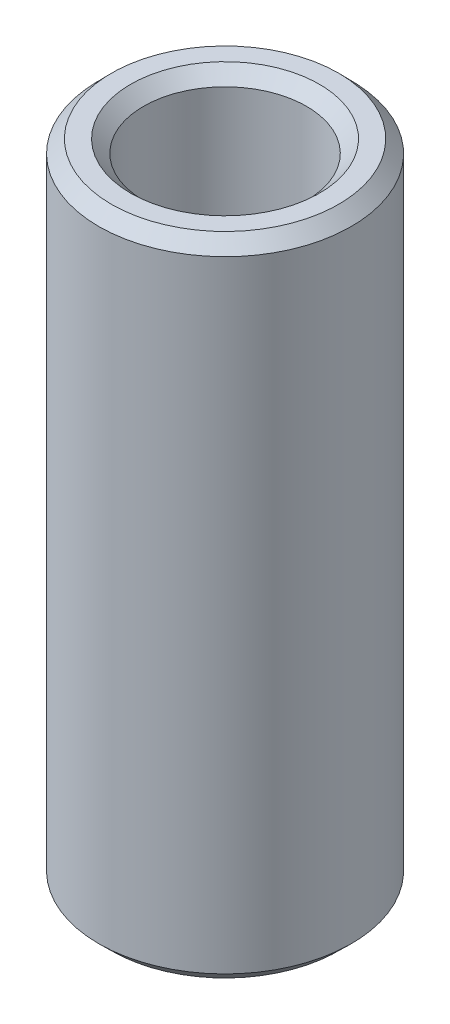
SolidWorks part; units mm, degrees
ref_plane "Front Plane" through (0, 0, 0) normal (0, 0, 1) x (1, 0, 0)
ref_plane "Top Plane" through (0, 0, 0) normal (0, 1, 0) x (1, 0, 0)
ref_plane "Right Plane" through (0, 0, 0) normal (1, 0, 0) x (0, 0, -1)
sketch "Sketch1" plane through (0, 0, 0) normal (0, 1, 0) x (1, 0, 0)
  circle A0 centre (0, 0) radius 7.5
  dimension "SLEEVE_OD" = 15
extrude "Boss-Extrude1" add sketch "Sketch1" along normal blind 38.4157
sketch "Sketch2" plane through (0, 0, 0) normal (0, 1, 0) x (1, 0, 0)
  circle A0 centre (0, 0) radius 4.8424
  dimension "BORE_D" = 9.6848
extrude "Cut-Extrude1" cut sketch "Sketch2" along normal through all
chamfer "Chamfer1" distance 0.7659 angle 44.426 4 edges at (0, 38.4157, 4.8424) (0, 0, 4.8424) (0, 0, 7.5) (0, 38.4157, 7.5) first distance on face at (0, 38.4157, 4.8424) first distance on face at (0, 0, 4.8424) first distance on face at (0, 38.4157, 7.5)
